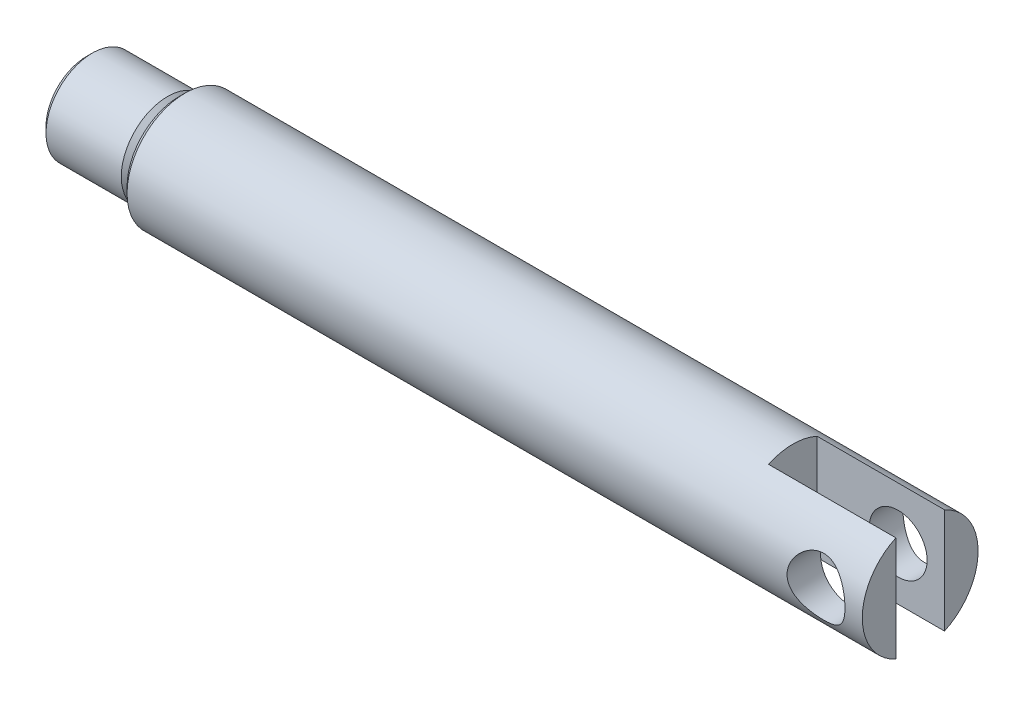
SolidWorks part; units mm, degrees
ref_plane "Front Plane" through (0, 0, 0) normal (0, 0, 1) x (1, 0, 0)
ref_plane "Top Plane" through (0, 0, 0) normal (0, 1, 0) x (1, 0, 0)
ref_plane "Right Plane" through (0, 0, 0) normal (1, 0, 0) x (0, 0, -1)
sketch "Sketch1" plane through (0, 0, 0) normal (0, 0, 1) x (1, 0, 0)
  line L0 (0, 0) -> (36, 0)
  line L1 (0, 0) -> (0, -2)
  line L2 (0, -2) -> (3.5, -2)
  line L3 (3.5, -2) -> (3.5, -1.75)
  line L4 (3.5, -1.75) -> (4, -1.75)
  line L5 (4, -1.75) -> (4, -2.5)
  line L6 (4, -2.5) -> (36, -2.5)
  line L7 (36, -2.5) -> (36, 0)
  point P8 (3.75, -1.75)
  dimension "D1" = 36
  dimension "D2" = 2
  dimension "D3" = 1.75
  dimension "D4" = 2.5
  dimension "D5" = 3.5
  dimension "D6" = 4
revolve "Revolve1" add sketch "Sketch1" angle 360 about L0
sketch "Sketch2" plane through (0, 0, 0) normal (0, 0, 1) x (1, 0, 0)
  line L0 (36, -2.5) -> (36, 2.5) construction
  circle A1 centre (34, 0) radius 1.25
  point P2 (0, 0)
  dimension "D1" = 2
extrude "Cut-Extrude1" cut sketch "Sketch2" against normal mid plane 10
sketch "Sketch3" plane through (36, 0, 0) normal (1, 0, 0) x (0, 0, -1)
  line L1 (-1.05, -5.5425) -> (1.05, -5.5425)
  line L2 (-1.05, -5.5425) -> (-1.05, 5.5425)
  line L3 (-1.05, 5.5425) -> (1.05, 5.5425)
  line L4 (1.05, -5.5425) -> (1.05, 5.5425)
  line L5 (-1.05, -5.5425) -> (1.05, 5.5425) construction
  line L6 (-1.05, 5.5425) -> (1.05, -5.5425) construction
  point P0 (0, 0)
  dimension "D1" = 2.1
extrude "Cut-Extrude2" cut sketch "Sketch3" against normal blind 5.5
chamfer "Chamfer1" distance 0.25 angle 45 3 edges at (0, 0, 2) (3.5, 0, 1.75) (4, 0, 2.5)
